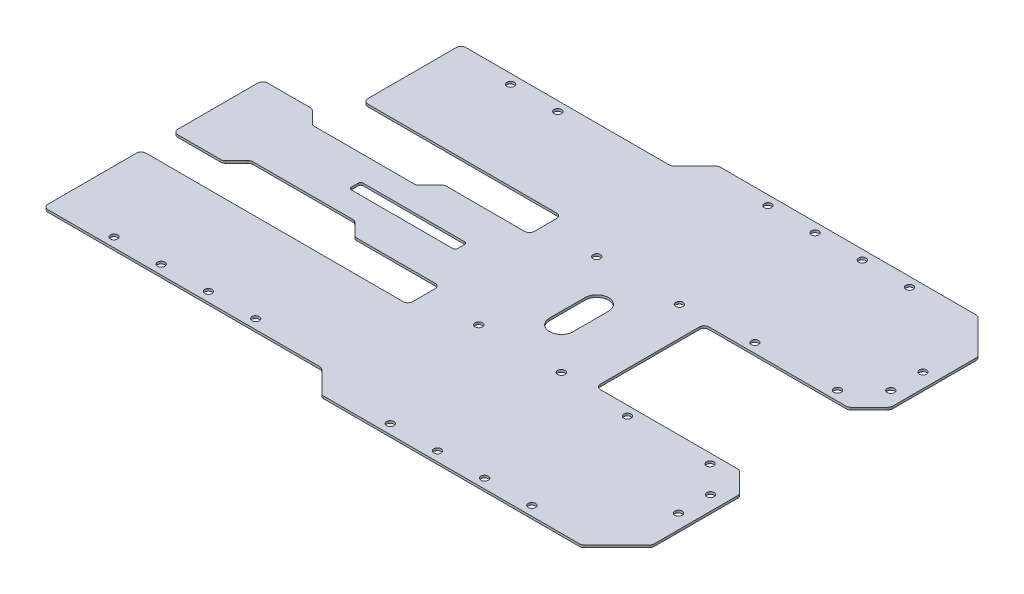
SolidWorks part; units mm, degrees
material "Thornel Mat VMA"
ref_plane "前视基准面" through (0, 0, 0) normal (0, 0, 1) x (1, 0, 0)
ref_plane "上视基准面" through (0, 0, 0) normal (0, 1, 0) x (1, 0, 0)
ref_plane "右视基准面" through (0, 0, 0) normal (1, 0, 0) x (0, 0, -1)
other "Configuration Table"
sketch "草图1" plane through (0, 0, 0) normal (0, 1, 0) x (1, 0, 0)
  line L1 (-13, 13) -> (13, 13) construction
  line L2 (-13, 13) -> (-13, -13) construction
  line L3 (-13, -13) -> (13, -13) construction
  line L4 (13, 13) -> (13, -13) construction
  line L5 (-13, 13) -> (13, -13) construction
  line L6 (-13, -13) -> (13, 13) construction
  line L7 (-35, 35) -> (35, 35)
  line L8 (-35, 35) -> (-35, -35)
  line L9 (-35, -35) -> (35, -35)
  line L10 (35, 35) -> (35, -35)
  line L11 (-35, 35) -> (35, -35) construction
  line L12 (-35, -35) -> (35, 35) construction
  circle A0 centre (13, -13) radius 1.6
  circle A1 centre (13, 13) radius 1.6
  circle A2 centre (-13, 13) radius 1.6
  circle A3 centre (-13, -13) radius 1.6
  point P0 (0, 0)
  point P10 (0, 0)
  dimension "D2" = 3.2
  dimension "D1" = 26
  dimension "D3" = 22
extrude "凸台-拉伸1" add sketch "草图1" along normal blind 1
sketch "草图2" plane through (0, 0, 0) normal (0, -1, 0) x (1, 0, 0)
  line L0 (35, -35) -> (35, -69)
  line L1 (35, -69) -> (20, -84)
  line L2 (20, -84) -> (-90, -84)
  line L3 (-90, -84) -> (-100, -74)
  line L4 (-100, -74) -> (-189, -74)
  line L5 (0, 0) -> (-22.8005, 0) construction
  line L6 (-100, 74) -> (-218, 74)
  line L7 (-90, 84) -> (-100, 74)
  line L8 (20, 84) -> (-90, 84)
  line L9 (35, 69) -> (20, 84)
  line L10 (35, 35) -> (35, 69)
  line L11 (-189, -74) -> (-189, -32.5)
  line L12 (-189, -32.5) -> (-105, -32.5)
  line L15 (-105, -32.5) -> (-105, 32.5)
  line L16 (-105, 32.5) -> (-218, 32.5)
  line L17 (-218, 32.5) -> (-218, 74)
  line L19 (35, 35) -> (-35, 35)
  line L20 (-35, 35) -> (-35, -35)
  line L21 (-35, -35) -> (35, -35)
  circle A0 centre (0, -50) radius 34 construction
  circle A3 centre (0, 50) radius 34 construction
  dimension "D3" = 68
  dimension "D1" = 135
  dimension "D2" = 50
  dimension "D4" = 135
  dimension "D5" = 10
  dimension "D6" = 110
  dimension "D7" = 224
  dimension "D8" = 65
  dimension "D9" = 32.5
  dimension "D10" = 253
  dimension "D11" = 140
  dimension "D12" = 15
extrude "凸台-拉伸2" add sketch "草图2" against normal blind 1
ref_plane "基准面1" through (0, 70, 0) normal (0, 1, 0) x (1, 0, 0)
sketch "草图3" plane through (0, 70, 0) normal (0, 1, 0) x (1, 0, 0)
  line L14 (35, -69) -> (35, 69)
  line L15 (35, 69) -> (20, 84)
  line L16 (20, 84) -> (-90, 84)
  line L17 (-90, 84) -> (-100, 74)
  line L18 (-100, 74) -> (-189, 74)
  line L19 (-189, 74) -> (-189, 32.5)
  line L20 (-189, 32.5) -> (-105, 32.5)
  line L21 (-105, 32.5) -> (-105, -32.5)
  line L22 (-105, -32.5) -> (-218, -32.5)
  line L23 (-218, -32.5) -> (-218, -74)
  line L24 (-218, -74) -> (-100, -74)
  line L25 (-100, -74) -> (-90, -84)
  line L26 (-90, -84) -> (20, -84)
  line L27 (20, -84) -> (35, -69)
  line L28 (35, -69) -> (35, 69)
  line L29 (35, 69) -> (20, 84)
  line L30 (20, 84) -> (-90, 84)
  line L31 (-90, 84) -> (-100, 74)
  line L32 (-100, 74) -> (-189, 74)
  line L33 (-189, 74) -> (-189, 32.5)
  line L34 (-189, 32.5) -> (-105, 32.5)
  line L35 (-105, 32.5) -> (-105, -32.5)
  line L36 (-105, -32.5) -> (-218, -32.5)
  line L37 (-218, -32.5) -> (-218, -74)
  line L38 (-218, -74) -> (-100, -74)
  line L39 (-100, -74) -> (-90, -84)
  line L40 (-90, -84) -> (20, -84)
  line L41 (20, -84) -> (35, -69)
  dimension "D1" = 0
extrude "凸台-拉伸3" [suppressed] add sketch "草图3" along normal blind 1 separate body
sketch "草图4" [suppressed] plane through (0, 70, 0) normal (0, -1, 0) x (1, 0, 0)
  line L0 (-58, 37.5) -> (-231, 37.5)
  line L1 (-231, 37.5) -> (-231, 71)
  line L2 (-231, 71) -> (-100.9745, 71)
  line L3 (-100.9745, 71) -> (-90.9745, 81)
  line L4 (-90.9745, 81) -> (10.5514, 81)
  line L5 (10.5514, 81) -> (32, 59.5514)
  line L6 (32, 59.5514) -> (32, -56.5959)
  line L7 (32, -56.5959) -> (7.5959, -81)
  line L8 (7.5959, -81) -> (-96.331, -81)
  line L9 (-96.331, -81) -> (-106.331, -71)
  line L10 (-106.331, -71) -> (-188, -71)
  line L11 (-188, -71) -> (-188, -37.5)
  line L12 (-188, -37.5) -> (-58, -37.5)
  line L13 (-58, -37.5) -> (-58, 37.5)
  line L14 (33, 62.2548) -> (13.2548, 82)
  line L15 (13.2548, 82) -> (-96.7452, 82)
  line L16 (-96.7452, 82) -> (-106.7452, 72)
  line L17 (-106.7452, 72) -> (-232, 72)
  line L18 (-232, 72) -> (-232, 36.5)
  line L19 (-232, 36.5) -> (-59, 36.5)
  line L20 (-59, 36.5) -> (-59, -36.5)
  line L21 (-59, -36.5) -> (-189, -36.5)
  line L22 (-189, -36.5) -> (-189, -72)
  line L23 (-189, -72) -> (-106.7452, -72)
  line L24 (-106.7452, -72) -> (-96.7452, -82)
  line L25 (-96.7452, -82) -> (13.2548, -82)
  line L26 (13.2548, -82) -> (33, -62.2548)
  line L27 (33, -62.2548) -> (33, 62.2548)
  line L28 (33, 62.2548) -> (13.2548, 82)
  line L29 (13.2548, 82) -> (-96.7452, 82)
  line L30 (-96.7452, 82) -> (-106.7452, 72)
  line L31 (-106.7452, 72) -> (-232, 72)
  line L32 (-232, 72) -> (-232, 36.5)
  line L33 (-232, 36.5) -> (-59, 36.5)
  line L34 (-59, 36.5) -> (-59, -36.5)
  line L35 (-59, -36.5) -> (-189, -36.5)
  line L36 (-189, -36.5) -> (-189, -72)
  line L37 (-189, -72) -> (-106.7452, -72)
  line L38 (-106.7452, -72) -> (-96.7452, -82)
  line L39 (-96.7452, -82) -> (13.2548, -82)
  line L40 (13.2548, -82) -> (33, -62.2548)
  line L41 (33, -62.2548) -> (33, 62.2548)
  dimension "D2" = 1
  dimension "D3" = 1
  dimension "D4" = 1
  dimension "D5" = 1
  dimension "D6" = 1
  dimension "D7" = 1
  dimension "D8" = 1
  dimension "D9" = 1
  dimension "D10" = 1
  dimension "D11" = 1
  dimension "D12" = 1
  dimension "D1" = 0
extrude "凸台-拉伸4" [suppressed] add sketch "草图4" along normal blind 50
sketch "草图5" plane through (0, 1, 0) normal (0, 1, 0) x (1, 0, 0)
  line L0 (-105, -32.5) -> (-105, 32.5) construction
  line L1 (-105, -15) -> (-218, -15)
  line L2 (-105, -15) -> (-105, 15)
  line L3 (-105, 15) -> (-218, 15)
  line L4 (-218, -15) -> (-218, 15)
  point P6 (-105, 0)
  dimension "D1" = 30
  dimension "D2" = 113
extrude "凸台-拉伸5" add sketch "草图5" against normal blind 1
sketch "草图6" plane through (0, 0, 0) normal (0, -1, 0) x (1, 0, 0)
  line L0 (-90, -84) -> (20, -84) construction
  line L1 (0, 0) -> (-45, 0) construction
  line L2 (-100, 74) -> (-218, 74) construction
  line L3 (-218, 74) -> (-218, 32.5) construction
  line L4 (-189, -74) -> (-100, -74) construction
  line L5 (-189, -32.5) -> (-189, -74) construction
  circle A0 centre (-5, -80) radius 1.55
  circle A1 centre (-25, -80) radius 1.55
  circle A2 centre (-65, -80) radius 1.55
  circle A3 centre (-45, -80) radius 1.55
  circle A4 centre (-45, 80) radius 1.55
  circle A5 centre (-65, 80) radius 1.55
  circle A6 centre (-25, 80) radius 1.55
  circle A7 centre (-5, 80) radius 1.55
  circle A8 centre (-164, -70) radius 1.55
  circle A9 centre (-192, 70) radius 1.55
  circle A10 centre (-172, 70) radius 1.55
  circle A11 centre (-152, 70) radius 1.55
  circle A12 centre (-132, 70) radius 1.55
  circle A13 centre (-144, -70) radius 1.55
  dimension "D1" = 20
  dimension "D2" = 3.1
  dimension "D4" = 45
  dimension "D5" = 20
  dimension "D7" = 4
  dimension "D8" = 26
  dimension "D10" = 20
  dimension "D11" = 4
  dimension "D12" = 25
  dimension "D3" = 4
  dimension "D6" = 45
  dimension "D13" = 20
  dimension "D9" = 4
extrude "切除-拉伸1" cut sketch "草图6" against normal blind 1
sketch "草图7" plane through (0, 0, 0) normal (0, -1, 0) x (1, 0, 0)
  line L0 (-218, 15) -> (-105, 15) construction
  line L1 (-218, 32.5) -> (-203, 32.5)
  line L2 (-218, 32.5) -> (-218, 15)
  line L3 (-218, 15) -> (-203, 15)
  line L4 (-203, 32.5) -> (-203, 15)
  line L5 (-218, -15) -> (-218, 15) construction
  line L6 (-218, 32.5) -> (-105, 32.5) construction
  dimension "D1" = 15
extrude "凸台-拉伸6" add sketch "草图7" against normal blind 1
sketch "草图8" plane through (0, 1, 0) normal (0, 1, 0) x (1, 0, 0)
  line L0 (0, 0) -> (-113.6725, 0) construction
  line L1 (-105, 15) -> (-145, 15)
  line L2 (-105, 15) -> (-105, 19)
  line L3 (-105, 19) -> (-145, 19)
  line L4 (-145, 15) -> (-145, 19)
  line L5 (-145, -15) -> (-145, -19)
  line L6 (-105, -19) -> (-145, -19)
  line L7 (-105, -15) -> (-105, -19)
  line L8 (-105, -15) -> (-145, -15)
  line L9 (-105, 15) -> (-218, 15) construction
  line L10 (-203, -15) -> (-191, -15)
  line L11 (-203, -15) -> (-203, -19)
  line L12 (-203, -19) -> (-191, -19)
  line L13 (-191, -15) -> (-191, -19)
  line L22 (-218, 15) -> (-191, 15)
  line L23 (-218, 15) -> (-218, 19)
  line L24 (-218, 19) -> (-191, 19)
  line L25 (-191, 15) -> (-191, 19)
  dimension "D1" = 4
  dimension "D2" = 40
  dimension "D4" = 12
extrude "凸台-拉伸7" add sketch "草图8" against normal blind 1
chamfer "倒角1" distance 4 angle 45 2 edges at (-145, 0.5, -19) (-145, 0.5, 19)
sketch "草图9" plane through (0, 1, 0) normal (0, 1, 0) x (1, 0, 0)
  line L0 (-218, -74) -> (-218, 19) construction
  line L1 (-203, -32.5) -> (-218, -32.5)
  line L2 (-203, -32.5) -> (-203, -19)
  line L3 (-203, -19) -> (-218, -19)
  line L4 (-218, -32.5) -> (-218, -19)
  line L5 (-203, -19) -> (-191, -19) construction
  line L6 (-145, -15) -> (-147, -13)
  line L7 (-147, -13) -> (-191, -13)
  line L8 (-191, -13) -> (-191, -15)
  line L9 (-191, -15) -> (-145, -15) construction
  line L10 (-145, -15) -> (-141, -19) construction
  line L11 (-145, -15) -> (-191, -15)
  line L12 (0, 0) -> (-236.0256, 0) construction
  line L13 (-145, 15) -> (-191, 15)
  line L14 (-191, 13) -> (-191, 15)
  line L15 (-147, 13) -> (-191, 13)
  line L16 (-145, 15) -> (-147, 13)
  dimension "D1" = 2
extrude "切除-拉伸2" cut sketch "草图9" against normal blind 1
chamfer "倒角2" distance 6 angle 45 2 edges at (-191, 0.5, -19) (-191, 0.5, 19)
sketch "草图10" plane through (0, 1, 0) normal (0, 1, 0) x (1, 0, 0)
  line L0 (35, -69) -> (35, 69) construction
  line L1 (-115, -2.5) -> (-160, -2.5)
  line L2 (-115, -2.5) -> (-115, 2.5)
  line L3 (-115, 2.5) -> (-160, 2.5)
  line L4 (-160, -2.5) -> (-160, 2.5)
  line L5 (-35, 23) -> (35, 23)
  line L6 (-35, 23) -> (-35, -23)
  line L7 (-35, -23) -> (35, -23)
  line L8 (35, 23) -> (35, -23)
  line L9 (-35, 23) -> (35, -23) construction
  line L10 (-35, -23) -> (35, 23) construction
  point P4 (-115, 0)
  point P6 (0, 0)
  dimension "D1" = 5
  dimension "D2" = 45
  dimension "D3" = 115
  dimension "D4" = 46
extrude "切除-拉伸3" cut sketch "草图10" against normal blind 10
fillet "圆角1" radius 1 4 edges at (-160, 0.5, 2.5) (-160, 0.5, -2.5) (-115, 0.5, 2.5) (-115, 0.5, -2.5)
sketch "草图11" plane through (0, 0, 0) normal (0, -1, 0) x (1, 0, 0)
  circle A0 centre (17.5, -27) radius 1.55
  circle A1 centre (17.5, 27) radius 1.55
  circle A2 centre (-17.5, 27) radius 1.55
  circle A3 centre (-17.5, -27) radius 1.55
  circle A4 centre (-47.5, 25) radius 1.55
  circle A5 centre (-47.5, -25) radius 1.55
  circle A6 centre (-82.5, -25) radius 1.55
  circle A7 centre (-82.5, 25) radius 1.55
  dimension "D1" = 3.1
extrude "切除-拉伸4" cut sketch "草图11" against normal blind 10
chamfer "倒角3" distance 9 angle 45 2 edges at (35, 0.5, 23) (35, 0.5, -23)
fillet "圆角2" radius 2 32 edges at (-35, 0.5, 23) (-35, 0.5, -23) (26, 0.5, -23) (35, 0.5, -32) (35, 0.5, -69) (20, 0.5, -84) (-90, 0.5, -84) (-100, 0.5, -74) (-189, 0.5, -74) (-189, 0.5, -32.5) (-105, 0.5, -32.5) (-105, 0.5, -19) (-141, 0.5, -19) (-147, 0.5, -13) (-191, 0.5, -13) (-197, 0.5, -19) (-218, 0.5, -19) (-218, 0.5, 19) (-197, 0.5, 19) (-191, 0.5, 13) (-147, 0.5, 13) (-141, 0.5, 19) (-105, 0.5, 32.5) (-218, 0.5, 32.5) (-218, 0.5, 74) (-100, 0.5, 74) (-90, 0.5, 84) (20, 0.5, 84) (35, 0.5, 69) (35, 0.5, 32) (26, 0.5, 23) (-105, 0.5, 19)
sketch "草图12" plane through (0, 0, 0) normal (0, -1, 0) x (1, 0, 0)
  circle A0 centre (28.9, 38.2) radius 1.55
  circle A1 centre (28.9, 51.8) radius 1.55
  circle A2 centre (28.9, -38.2) radius 1.55
  circle A3 centre (28.9, -51.8) radius 1.55
  dimension "D1" = 3.1
extrude "切除-拉伸5" cut sketch "草图12" against normal blind 5
sketch "草图13" plane through (0, 0, 0) normal (0, -1, 0) x (1, 0, 0)
  line L0 (-65, 7.5) -> (-65, -7.5) construction
  line L1 (-60, 7.5) -> (-60, -7.5)
  line L2 (-70, 7.5) -> (-70, -7.5)
  line L4 (-82.5, 25) -> (-47.5, 25) construction
  line L5 (-82.5, 25) -> (-82.5, -25) construction
  line L6 (-82.5, -25) -> (-47.5, -25) construction
  line L7 (-47.5, 25) -> (-47.5, -25) construction
  arc A0 (-60, 7.5) -> (-70, 7.5) centre (-65, 7.5) ccw
  arc A1 (-70, -7.5) -> (-60, -7.5) centre (-65, -7.5) ccw
  point P2 (-65, 0)
  point P7 (-47.5, 0)
  point P15 (-65, 25)
  dimension "D1" = 5
  dimension "D2" = 15
extrude "切除-拉伸6" cut sketch "草图13" against normal blind 10
